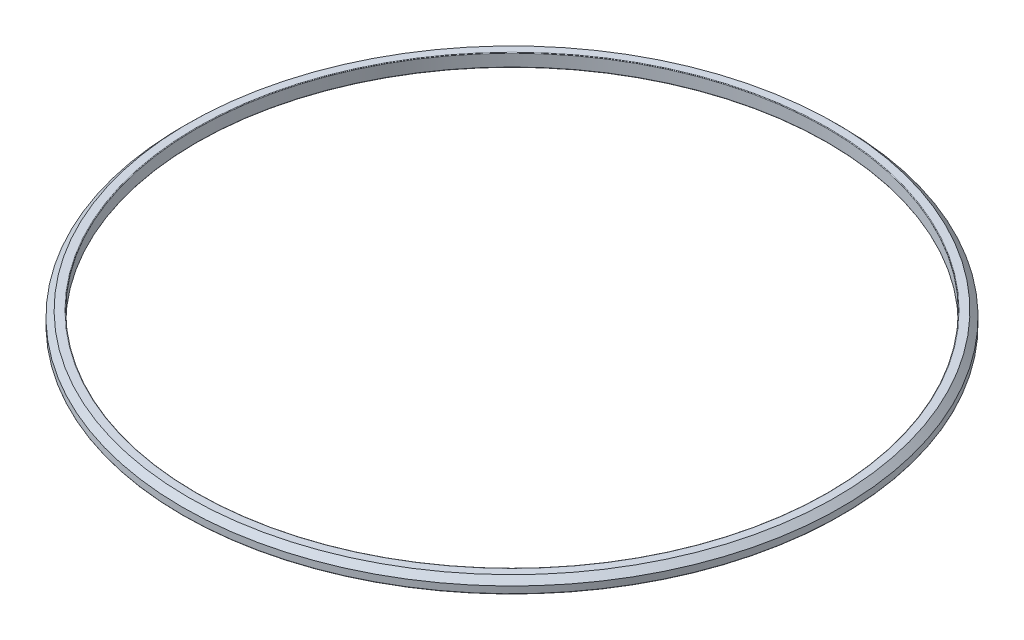
SolidWorks part; units mm, degrees
material "PETG"
ref_plane "Front Plane" through (0, 0, 0) normal (0, 0, 1) x (1, 0, 0)
ref_plane "Top Plane" through (0, 0, 0) normal (0, 1, 0) x (1, 0, 0)
ref_plane "Right Plane" through (0, 0, 0) normal (1, 0, 0) x (0, 0, -1)
sketch "Sketch1" plane through (0, 0, 0) normal (0, 1, 0) x (1, 0, 0)
  circle A0 centre (0, 0) radius 57.2125
  circle A1 centre (0, 0) radius 54.7875
  dimension "Ring OD" = 114.425
  dimension "Ring ID" = 109.575
extrude "Boss-Extrude1" add sketch "Sketch1" along normal blind 2.25
chamfer "Chamfer1" distance 1 angle 45 1 edges at (0, 2.25, 57.2125)
fillet "Fillet1" radius 0.1 3 edges at (0, 2.25, 54.7875) (0, 0, 54.7875) (0, 0, 57.2125)
equation "\"tol_dia_id_intfc\" = 0.0500mm ' For hole diameters - Interference fit"
equation "\"tol_dia_id_slip\"  = 0.0750mm ' For hole diameters - Slip fit"
equation "\"tol_dia_id_clear\" = 0.1000mm ' For hole diameters - Clearance fit"
equation "\"tol_dia_od_intfc\" = 0.0500mm ' For shaft diameters - Interference fit"
equation "\"tol_dia_od_slip\"  = 0.0750mm ' For shaft diameters - Slip fit"
equation "\"tol_dia_od_clear\" = 0.1000mm ' For shaft diameters - Clearance fit"
equation "\"tol_general_intfc\"= 0.0250mm ' For general parts (Horiz) - Interference fit"
equation "\"tol_general_slip\" = 0.0375mm ' For general parts (Horiz) - Slip fit"
equation "\"tol_general_clear\"= 0.0500mm ' For general parts (Horiz) - Clearance fit"
equation "\"tol_layer_intfc\"  = 0.0250mm ' For all parts (Vert) - Interference fit"
equation "\"tol_layer_slip\"   = 0.0375mm ' For all parts (Vert) - Slip fit"
equation "\"tol_layer_clear\"  = 0.0500mm ' For all parts (Vert) - Clearance fit"
equation "\"tol_corner_rad\"   = 0.100mm ' For corners that fit into other parts"
equation "\"Ring OD@Sketch1\"= 114.50mm - \"tol_dia_od_slip\""
equation "\"Ring ID@Sketch1\" = 114.5 - ( 2.5 * 2 ) + \"tol_dia_id_slip\""
equation "\"D1@Fillet1\"=\"tol_corner_rad\""
